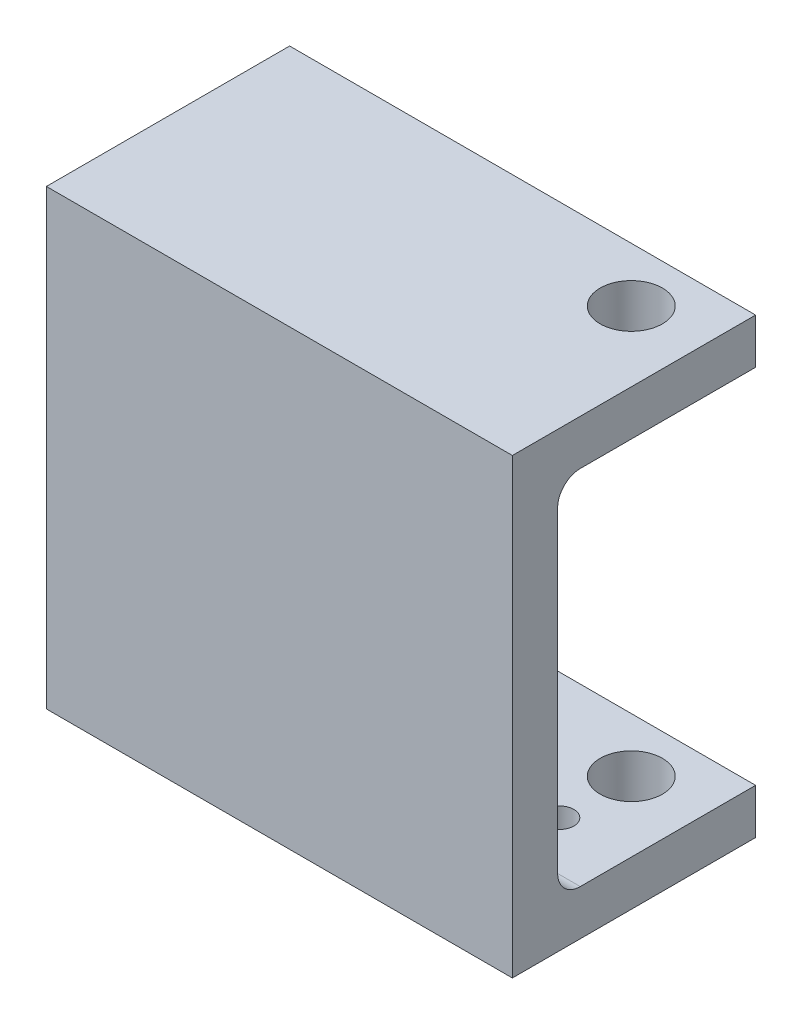
SolidWorks part; units mm, degrees
ref_plane "Front Plane" through (0, 0, 0) normal (0, 0, 1) x (1, 0, 0)
ref_plane "Top Plane" through (0, 0, 0) normal (0, 1, 0) x (1, 0, 0)
ref_plane "Right Plane" through (0, 0, 0) normal (1, 0, 0) x (0, 0, -1)
sketch "Sketch1" plane through (0, 0, 0) normal (0, 0, 1) x (1, 0, 0)
  line L1 (-22.5, 20) -> (22.5, 20)
  line L2 (-22.5, 20) -> (-22.5, -20)
  line L3 (-22.5, -20) -> (22.5, -20)
  line L4 (22.5, 20) -> (22.5, -20)
  line L5 (-22.5, 20) -> (22.5, -20) construction
  line L6 (-22.5, -20) -> (22.5, 20) construction
  point P0 (0, 0)
  dimension "D1" = 40
  dimension "D2" = 45
extrude "Boss-Extrude1" add sketch "Sketch1" along normal blind 4
sketch "Sketch2" plane through (0, 0, 0) normal (0, 0, -1) x (-1, 0, 0)
  line L0 (-22.5, -20) -> (-22.5, 20) construction
  line L1 (22.5, 20) -> (-22.5, 20)
  line L2 (22.5, 20) -> (22.5, 16)
  line L3 (22.5, 16) -> (-22.5, 16)
  line L4 (-22.5, 20) -> (-22.5, 16)
  line L5 (22.5, 0) -> (-22.5, 0) construction
  line L6 (22.5, 20) -> (22.5, -20) construction
  line L7 (22.5, -16) -> (-22.5, -16)
  line L8 (-22.5, -20) -> (-22.5, -16)
  line L9 (22.5, -20) -> (-22.5, -20)
  line L10 (22.5, -20) -> (22.5, -16)
  dimension "D1" = 4
extrude "Boss-Extrude2" add sketch "Sketch2" along normal blind 17.5
sketch "Sketch5" plane through (22.5, 0, 0) normal (1, 0, 0) x (0, 0, -1)
  line L1 (3.81, -6.35) -> (-3.81, -6.35)
  line L2 (3.81, -6.35) -> (3.81, 6.35)
  line L3 (3.81, 6.35) -> (-3.81, 6.35)
  line L4 (-3.81, -6.35) -> (-3.81, 6.35)
  line L5 (3.81, -6.35) -> (-3.81, 6.35) construction
  line L6 (3.81, 6.35) -> (-3.81, -6.35) construction
  line L7 (0, -16) -> (0, 16) construction
  point P6 (0, 0)
  point P7 (0, 0)
  dimension "D1" = 12.7
  dimension "D2" = 7.62
extrude "Cut-Extrude2" [suppressed] cut sketch "Sketch5" against normal blind 7.62
sketch "Sketch6" [suppressed] plane through (0, 0, 3.81) normal (0, 0, -1) x (-1, 0, 0)
  line L1 (-11.43, 6.35) -> (-19.05, 6.35) construction
  line L2 (-19.05, 6.35) -> (-19.05, -6.35) construction
  line L4 (-16.51, 6.35) -> (-19.05, 6.35)
  line L5 (0, 0) -> (-19.05, 0) construction
  line L9 (-19.05, 6.35) -> (-19.05, 4.826)
  line L10 (-19.05, 4.826) -> (-16.51, 4.559)
  line L11 (-16.51, 4.559) -> (-16.51, 6.35)
  line L12 (-19.05, -6.35) -> (-19.05, -4.826)
  line L13 (-19.05, -4.826) -> (-16.51, -4.559)
  line L14 (-16.51, -4.559) -> (-16.51, -6.35)
  line L15 (-16.51, -6.35) -> (-19.05, -6.35)
  dimension "D1" = 2.54
  dimension "D2" = 6
  dimension "D3" = 1.524
extrude "Boss-Extrude3" [suppressed] add sketch "Sketch6" along normal up to surface (3.81 mm away) from surface up to face at (0, 0, 0)
sketch "Sketch7" plane through (0, -20, 0) normal (0, -1, 0) x (1, 0, 0)
  line L0 (22.5, 4) -> (22.5, -17.5) construction
  line L2 (-22.5, 0) -> (22.5, 0) construction
  circle A0 centre (12.5, -12.7) radius 2.75
  circle A1 centre (12.5, -6.35) radius 1.275
  dimension "D1" = 5.5
  dimension "D4" = 2.55
  dimension "D2" = 10
  dimension "D3" = 12.7
  dimension "D5" = 6.35
extrude "Cut-Extrude3" cut sketch "Sketch7" against normal up to surface (40 mm away) contours A0 region at (12.5, -20, -12.7) up to face at (0, 20, -6.75)
extrude "Cut-Extrude4" cut sketch "Sketch7<4>" against normal up to surface (4 mm away) contours A1 region at (12.5, -20, -6.35) up to face at (15.25, -16, -12.7)
sketch "Sketch7<4>" plane through (0, -20, 0) normal (0, -1, 0) x (1, 0, 0) same geometry as "Sketch7"
fillet "Fillet1" radius 2 2 edges at (0, -16, 0) (0, 16, 0)
sketch "Sketch8" plane through (0, -20, 0) normal (0, -1, 0) x (1, 0, 0)
  line L0 (-22.5, 4) -> (22.5, 4) construction
  line L1 (22.5, -17.5) -> (18.69, -17.5)
  line L2 (22.5, -17.5) -> (22.5, 4)
  line L3 (22.5, 4) -> (18.69, 4)
  line L4 (18.69, -17.5) -> (18.69, 4)
  dimension "D1" = 3.81
extrude "Cut-Extrude5" cut sketch "Sketch8" against normal through all
sketch "Sketch9" plane through (0, 0, 0) normal (0, 0, -1) x (-1, 0, 0)
  line L0 (8.5, 16) -> (8.5, -17.5474) construction
  line L4 (-18.69, -20) -> (22.5, -20) construction
  line L5 (22.5, 20) -> (-18.69, 20) construction
  circle A0 centre (8.5, 8) radius 4
  circle A1 centre (8.5, -8) radius 4
  point P2 (-40.0361, 6.9513)
  point P14 (8.5, 16)
  point P15 (0, 0)
  dimension "D2" = 8
  dimension "D3" = 8
  dimension "D4" = 12
  dimension "D5" = 12
extrude "Cut-Extrude6" cut sketch "Sketch9" against normal blind 2
